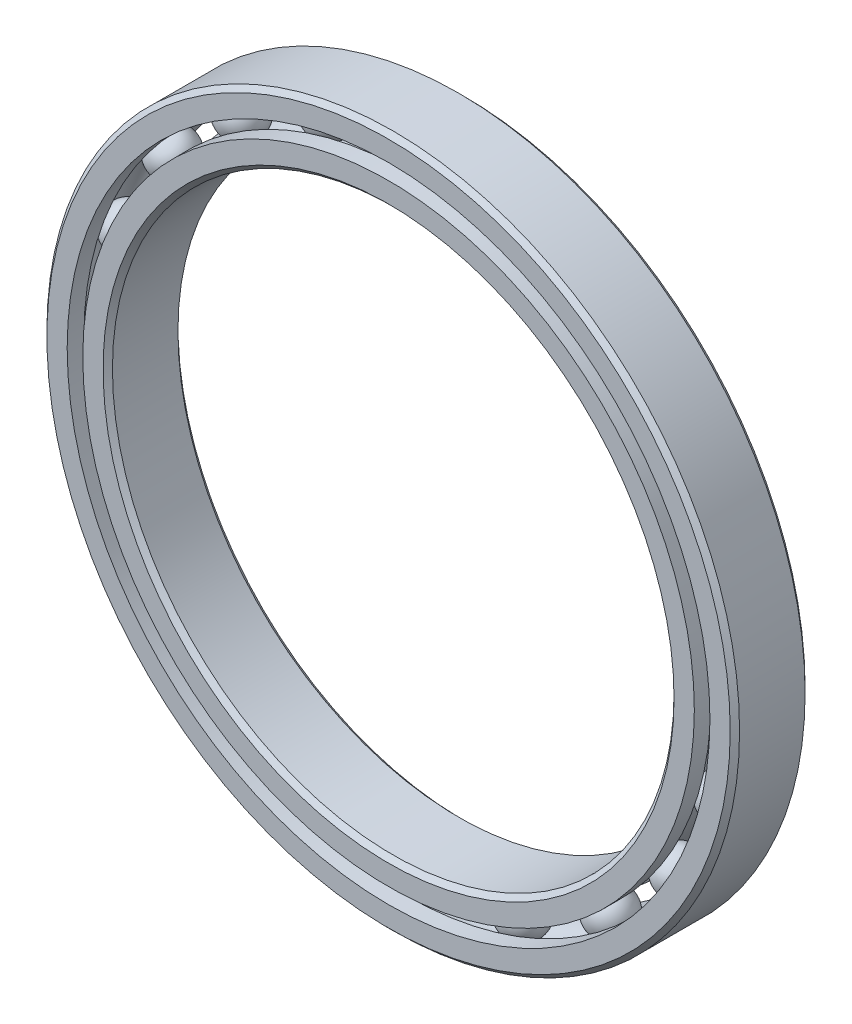
SolidWorks part; units mm, degrees
ref_plane "Front Plane" through (0, 0, 0) normal (0, 0, 1) x (1, 0, 0)
ref_plane "Top Plane" through (0, 0, 0) normal (0, 1, 0) x (1, 0, 0)
ref_plane "Right Plane" through (0, 0, 0) normal (1, 0, 0) x (0, 0, -1)
sketch "Sketch1" plane through (0, 0, 0) normal (1, 0, 0) x (0, 0, -1)
  line L0 (-2, 0) -> (2, 0) construction
  line L1 (0, 18.5) -> (0, -18.5) construction
  line L2 (1.75, 18.5) -> (-1.75, 18.5)
  line L3 (-1.75, 18.5) -> (-2, 18.25)
  line L4 (-2, 18.25) -> (-2, 17.1668)
  line L5 (-2, 17.1668) -> (-1.1111, 17.1668)
  line L6 (2, 17.1668) -> (1.1111, 17.1668)
  line L7 (2, 18.25) -> (2, 17.1668)
  line L8 (1.75, 18.5) -> (2, 18.25)
  line L9 (0, 18.5) -> (0, 16.75) construction
  line L10 (0, 16.75) -> (0, 15) construction
  arc A0 (-1.1111, 17.1668) -> (1.1111, 17.1668) centre (0, 16.75) cw
  point P14 (0, 15)
  dimension "Width" = 4
  dimension "OD" = 37
  dimension "D1" = 45
  dimension "D2" = 0.25
  dimension "Shaft Dia" = 30
  dimension "D3" = 2.2222
revolve "Revolve1" add sketch "Sketch1" angle 360 about L0
sketch "Sketch3" plane through (0, 0, 0) normal (1, 0, 0) x (0, 0, -1)
  line L0 (-2, 16.3332) -> (-1.1111, 16.3332)
  line L1 (0, 18.5) -> (0, -18.5) construction
  line L2 (-2, 18.25) -> (-2, 17.1668) construction
  line L3 (-2, 16.3332) -> (-2, 15.25)
  line L4 (-1.75, 18.5) -> (-2, 18.25) construction
  line L5 (-2, 15.25) -> (-1.75, 15)
  line L6 (-1.75, 15) -> (1.75, 15)
  line L7 (1.75, 18.5) -> (1.75, -18.5) construction
  line L8 (1.75, 15) -> (2, 15.25)
  line L9 (2, -18.25) -> (2, 18.25) construction
  line L10 (2, 15.25) -> (2, 16.3332)
  line L11 (2, 16.3332) -> (1.1111, 16.3332)
  line L13 (1.75, 18.5) -> (2, 18.25) construction
  arc A0 (1.1111, 17.1668) -> (-1.1111, 17.1668) centre (0, 16.75) ccw construction
  arc A1 (1.1111, 16.3332) -> (-1.1111, 16.3332) centre (0, 16.75) cw
revolve "Revolve3" add sketch "Sketch3" angle 360 about L0
sketch "Sketch4" plane through (0, 0, 0) normal (1, 0, 0) x (0, 0, -1)
  line L0 (-1.1867, 16.75) -> (1.1867, 16.75)
  arc A2 (-1.1867, 16.75) -> (1.1867, 16.75) centre (0, 16.75) cw
  arc A3 (1.1111, 17.1668) -> (-1.1111, 17.1668) centre (0, 16.75) ccw construction
revolve "Revolve4" add sketch "Sketch4" angle 360 about L0
ref_axis "Axis1" through (0, 0, -2) along (0, 0, 1)
pattern_circular "CirPattern1" count 20 over 360 about axis through (0, 0, -2) along (0, 0, 1) of bodies 104
sketch "Sketch5" plane through (0, 0, 0) normal (1, 0, 0) x (0, 0, -1)
  line L0 (-2, 17.1668) -> (-1.1111, 17.1668) construction
  line L1 (-1.875, 17.1668) -> (-1.1867, 17.1668)
  line L2 (-1.875, 17.1668) -> (-1.875, 16.3332)
  line L3 (-1.875, 16.3332) -> (-1.1867, 16.3332)
  line L4 (-1.1867, 17.1668) -> (-1.1867, 16.3332)
  line L5 (-2, 16.3332) -> (-1.1111, 16.3332) construction
  line L6 (2, 17.1668) -> (1.1111, 17.1668) construction
  line L7 (1.875, 17.1668) -> (1.1867, 17.1668)
  line L8 (1.875, 17.1668) -> (1.875, 16.3332)
  line L9 (1.875, 16.3332) -> (1.1867, 16.3332)
  line L10 (1.1867, 17.1668) -> (1.1867, 16.3332)
  line L11 (2, 16.3332) -> (1.1111, 16.3332) construction
  line L12 (-1.75, 18.5) -> (-2, 18.25) construction
  point P18 (-1.875, 18.375)
equation "\"D2@Sketch1\" = \"Width@Sketch1\"*.05"
equation "\"D3@Sketch1\" = \"Width@Sketch1\"/2.25"
